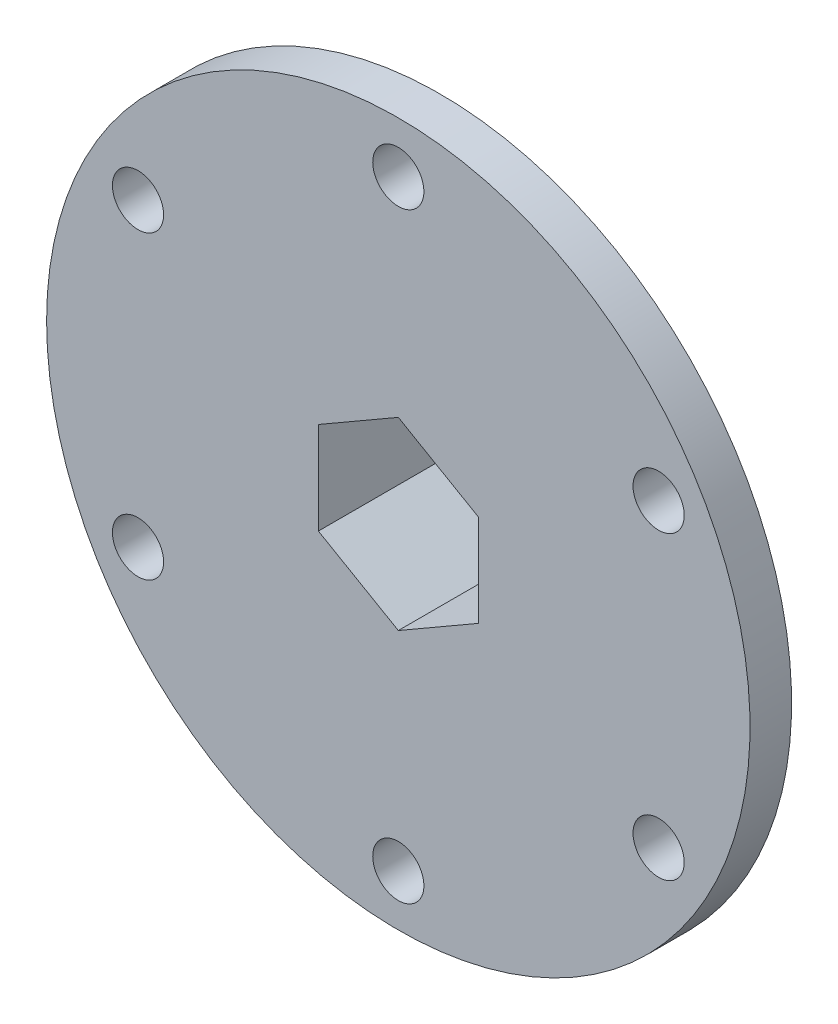
SolidWorks part; units mm, degrees
material "6061 Alloy"
ref_plane "Front Plane" through (0, 0, 0) normal (0, 0, 1) x (1, 0, 0)
ref_plane "Top Plane" through (0, 0, 0) normal (0, 1, 0) x (1, 0, 0)
ref_plane "Right Plane" through (0, 0, 0) normal (1, 0, 0) x (0, 0, -1)
sketch "Sketch1" plane through (0, 0, 0) normal (0, 0, 1) x (1, 0, 0)
  line L0 (0, 0) -> (0, 23.876) construction
  line L1 (0, -7.3323) -> (6.35, -3.6662) construction
  line L2 (6.35, -3.6662) -> (6.35, 3.6662) construction
  line L3 (6.35, 3.6662) -> (0, 7.3323) construction
  line L4 (0, 7.3323) -> (-6.35, 3.6662) construction
  line L5 (-6.35, 3.6662) -> (-6.35, -3.6662) construction
  line L6 (-6.35, -3.6662) -> (0, -7.3323) construction
  circle A0 centre (0, 0) radius 27.94
  circle A1 centre (0, 0) radius 6.35 construction
  circle A2 centre (0, 23.876) radius 2.032
  circle A3 centre (20.6772, 11.938) radius 2.032
  circle A4 centre (20.6772, -11.938) radius 2.032
  circle A5 centre (0, -23.876) radius 2.032
  circle A6 centre (-20.6772, -11.938) radius 2.032
  circle A7 centre (-20.6772, 11.938) radius 2.032
  point P25 (0, 0)
  dimension "D2" = 55.88
  dimension "D3" = 4.064
  dimension "D4" = 23.876
  dimension "D5" = 12.7
  dimension "D1" = 6
extrude "Boss-Extrude1" add sketch "Sketch1" along normal blind 3.302
sketch "Sketch2" plane through (0, 0, 0) normal (0, 0, -1) x (-1, 0, 0)
  circle A0 centre (0, 0) radius 14.224
  dimension "D1" = 28.448
extrude "Boss-Extrude2" add sketch "Sketch2" along normal blind 9.398
sketch "Sketch3" plane through (0, 0, -9.398) normal (0, 0, -1) x (-1, 0, 0)
  line L0 (0, 0) -> (0, 23.876) construction
  line L1 (0, 7.3323) -> (-6.35, 3.6662)
  line L2 (-6.35, 3.6662) -> (-6.35, -3.6662)
  line L3 (-6.35, -3.6662) -> (0, -7.3323)
  line L4 (0, -7.3323) -> (6.35, -3.6662)
  line L5 (6.35, -3.6662) -> (6.35, 3.6662)
  line L6 (6.35, 3.6662) -> (0, 7.3323)
  circle A0 centre (0, 0) radius 6.35 construction
  dimension "D1" = 12.7
extrude "Cut-Extrude1" cut sketch "Sketch3" against normal up to surface (12.7 mm away) up to face at (-18.6452, -11.938, 3.302)
